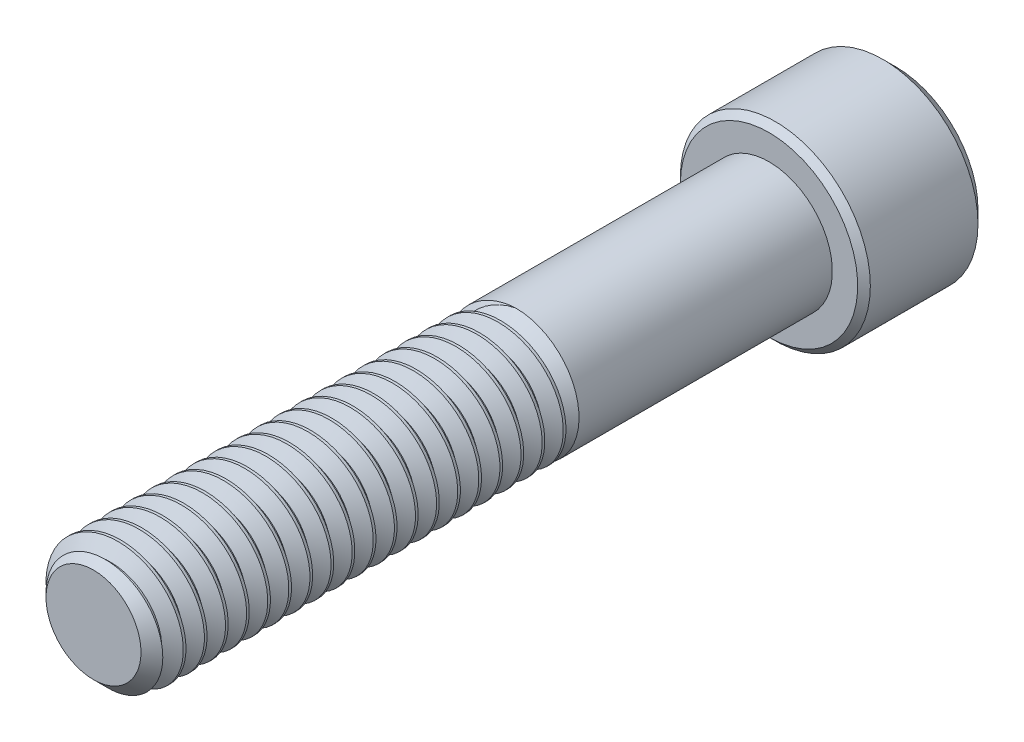
SolidWorks part; units mm, degrees
material "Cast Alloy Steel"
ref_plane "Front Plane" through (0, 0, 0) normal (0, 0, 1) x (1, 0, 0)
ref_plane "Top Plane" through (0, 0, 0) normal (0, 1, 0) x (1, 0, 0)
ref_plane "Right Plane" through (0, 0, 0) normal (1, 0, 0) x (0, 0, -1)
sketch "Sketch1" plane through (0, 0, 0) normal (0, 0, 1) x (1, 0, 0)
  line L0 (0, 4.7625) -> (0, -4.7625) construction
  circle A0 centre (0, 0) radius 4.7625
  dimension "OD" = 9.525
extrude "Extrude1" add sketch "Sketch1" against normal blind 50.8
sketch "Sketch2" plane through (0, 0, 0) normal (0, 0, 1) x (1, 0, 0)
  circle A0 centre (0, 0) radius 4.7625 construction
  circle A1 centre (0, 0) radius 4.7625
curve "Helix/Spiral1" pitch 1.5875 height 34.925 turns 22 parameters "pitch"=1.5875
chamfer "Chamfer3" distance 1.1906 angle 45 1 edges at (4.7625, 0, 0)
sketch "Sketch3" plane through (0, 0, 0) normal (1, 0, 0) x (0, 0, -1)
  line L0 (-1.3891, 4.7625) -> (-0.7938, 3.7314)
  line L1 (-0.7938, 3.7314) -> (-0.5953, 3.7314)
  line L2 (-0.5953, 3.7314) -> (0, 4.7625)
  line L3 (-1.3891, 4.7625) -> (0, 4.7625)
  line L4 (-0.6945, 4.7625) -> (-0.6945, 3.7314) construction
  line L5 (-1.0914, 4.2469) -> (-0.2977, 4.2469) construction
  line L6 (0, 4.7625) -> (0, -4.7625) construction
  dimension "D1" = 0.1984
  dimension "D2" = 0.7937
  dimension "D3" = 60
sweep "Cut-Sweep1" cut profiles "Sketch3" path "Helix/Spiral1"
sketch "Sketch5" plane through (0, 0, 0) normal (1, 0, 0) x (0, 0, -1)
  line L1 (50.8, 4.7625) -> (31.75, 4.7625)
  line L2 (50.8, 4.7625) -> (50.8, 0)
  line L3 (50.8, 0) -> (31.75, 0)
  line L4 (31.75, 4.7625) -> (31.75, 0) construction
  line L6 (0, 0) -> (9.9695, 0) construction
  line L8 (31.75, 4.7625) -> (26.9875, 0)
  line L9 (26.9875, 0) -> (31.75, 0)
  line L10 (50.8, -4.7625) -> (50.8, 4.7625) construction
  dimension "D1" = 45
  dimension "Thread min" = 31.75
revolve "partially thread" add sketch "Sketch5" angle 360 about L6
sketch "Sketch6" plane through (0, 0, -50.8) normal (0, 0, -1) x (-1, 0, 0)
  circle A0 centre (0, 0) radius 7.1438
  dimension "head dia" = 14.2875
extrude "Extrude2" add sketch "Sketch6" along normal blind 9.525
sketch "Sketch7" plane through (0, 0, -60.325) normal (0, 0, -1) x (-1, 0, 0)
  line L1 (0, 4.5827) -> (-3.9688, 2.2914)
  line L2 (-3.9688, 2.2914) -> (-3.9688, -2.2914)
  line L3 (-3.9688, -2.2914) -> (0, -4.5827)
  line L4 (0, -4.5827) -> (3.9688, -2.2914)
  line L5 (3.9688, -2.2914) -> (3.9688, 2.2914)
  line L6 (3.9688, 2.2914) -> (0, 4.5827)
  circle A0 centre (0, 0) radius 3.9688 construction
  dimension "hex dia" = 7.9375
extrude "Cut-Extrude1" cut sketch "Sketch7" against normal blind 5.9531
sketch "Sketch8" plane through (0, 0, -60.325) normal (0, 0, -1) x (-1, 0, 0)
  circle A0 centre (0, 0) radius 4.5827
extrude "Cut-Extrude2" cut sketch "Sketch8" against normal blind 0.9525 draft 45
chamfer "Chamfer1" distance 0.9525 angle 45 1 edges at (-7.1438, 0, -60.325)
chamfer "Chamfer2" distance 0.4763 angle 45 1 edges at (-7.1438, 0, -50.8)
sketch "Sketch9" plane through (0, 0, 0) normal (1, 0, 0) x (0, 0, -1)
  line L0 (0, 4.7625) -> (0, -4.7625) construction
  line L1 (8.7312, 4.7625) -> (8.7312, -4.7625) construction
  line L2 (50.8, 7.1437) -> (50.8, -7.1438) construction
  line L3 (60.325, 7.1437) -> (60.325, -7.1438) construction
  line L4 (60.325, 0) -> (0, 0) construction
  line L5 (61.6852, 4.7625) -> (61.6852, -4.7625) construction
  dimension "D1" = 8.7312
  dimension "D2" = 9.525
  dimension "D3" = 14.2875
  dimension "D4" = 50.8
  dimension "Thread Length" = 61.6852
equation "\"D3@Helix/Spiral1\" = \"Thread min@Sketch5\"+(\"pitch@Helix/Spiral1\"*2)"
equation "\"D1@Sketch3\" = \"pitch@Helix/Spiral1\"*.125"
equation "\"D2@Sketch3\" = \"pitch@Helix/Spiral1\"*.5"
equation "\"D1@Cut-Extrude1\" = \"hex dia@Sketch7\"*.75"
equation "\"D1@Chamfer1\" = \"head depth@Extrude2\"/10"
equation "\"D1@Sketch9\" = \"pitch@Helix/Spiral1\"*5.5"
equation "\"D1@Chamfer2\" = \"D1@Chamfer1\"/2"
equation "\"D1@Cut-Extrude2\" = \"D1@Chamfer2\"*2"
equation "\"D1@Chamfer3\" = \"pitch@Helix/Spiral1\"*.750"
equation "\"D2@Sketch9\" = \"head depth@Extrude2\""
equation "\"D3@Sketch9\" = \"head dia@Sketch6\""
equation "\"D4@Sketch9\" = \"screw length@Extrude1\""
